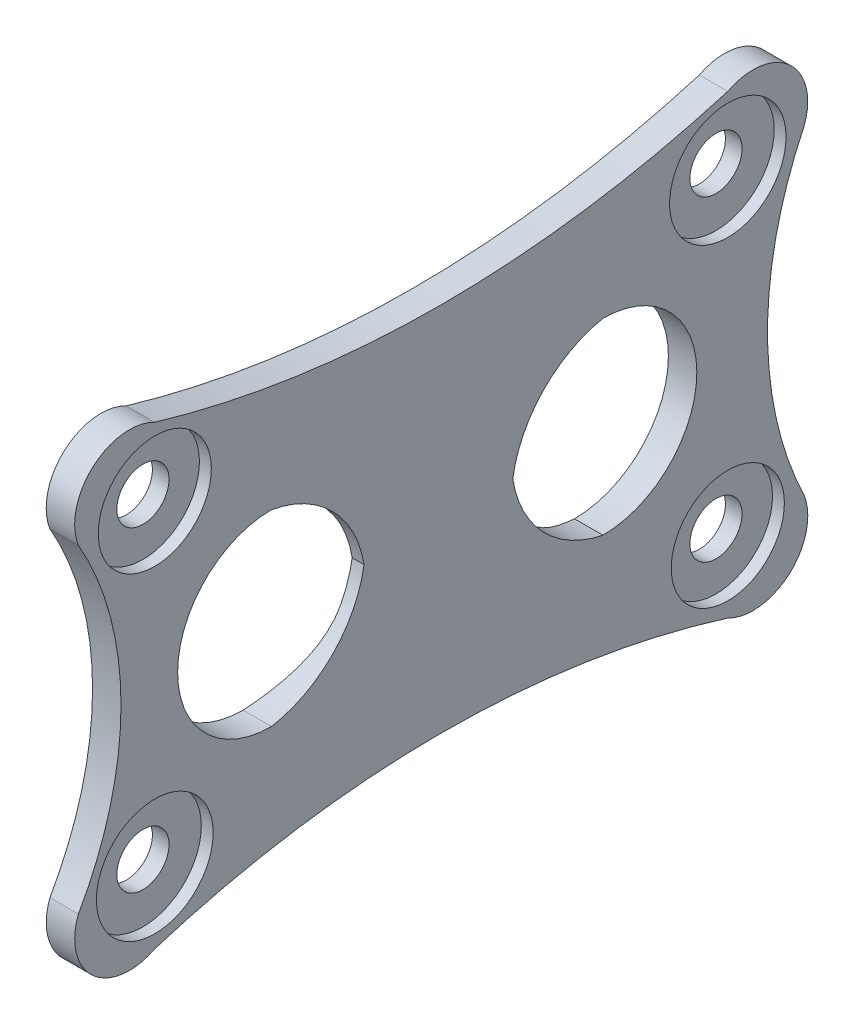
SolidWorks part; units mm, degrees
ref_plane "前视基准面" through (0, 0, 0) normal (0, 0, 1) x (1, 0, 0)
ref_plane "上视基准面" through (0, 0, 0) normal (0, 1, 0) x (1, 0, 0)
ref_plane "右视基准面" through (0, 0, 0) normal (1, 0, 0) x (0, 0, -1)
sketch "草图1" plane through (0, 0, 0) normal (1, 0, 0) x (0, 0, -1)
  line L1 (-37.5961, 46.5132) -> (45.4039, 46.5132)
  line L2 (-37.5961, 46.5132) -> (-37.5961, -12.4868)
  line L3 (-37.5961, -12.4868) -> (45.4039, -12.4868)
  line L4 (45.4039, 46.5132) -> (45.4039, -12.4868)
  line L5 (-39.5961, 48.5132) -> (47.4039, 48.5132)
  line L6 (-39.5961, 48.5132) -> (-39.5961, -14.4868)
  line L7 (-39.5961, -14.4868) -> (47.4039, -14.4868)
  line L8 (47.4039, 48.5132) -> (47.4039, -14.4868)
  dimension "D1" = 83
  dimension "D2" = 59
  dimension "D3" = 2
  dimension "D4" = 2
  dimension "D5" = 2
  dimension "D6" = 2
extrude "凸台-拉伸1" add sketch "草图1" along normal blind 5
sketch "草图2" plane through (5, 0, 0) normal (1, 0, 0) x (0, 0, -1)
  line L1 (-39.5961, 48.5132) -> (47.4039, 48.5132)
  line L2 (-39.5961, 48.5132) -> (-39.5961, -14.4868)
  line L3 (-39.5961, -14.4868) -> (47.4039, -14.4868)
  line L4 (47.4039, 48.5132) -> (47.4039, -14.4868)
extrude "凸台-拉伸2" add sketch "草图2" along normal blind 3
sketch "草图3" plane through (0, 0, -47.4039) normal (0, 0, -1) x (-1, 0, 0)
  line L1 (-5.0451, -4.4807) -> (-2.2805, -4.4807)
  line L2 (-5.0451, -4.4807) -> (-5.0451, -9.1322)
  line L3 (-5.0451, -9.1322) -> (-2.2805, -9.1322)
  line L4 (-2.2805, -4.4807) -> (-2.2805, -9.1322)
extrude "切除-拉伸1" cut sketch "草图3" against normal blind 2
fillet "圆角1" radius 2 8 edges at (4, 48.5132, -47.4039) (4, -14.4868, -47.4039) (4, -14.4868, 39.5961) (4, 48.5132, 39.5961) (8, 48.5132, -3.9039) (8, 17.0132, -47.4039) (8, -14.4868, -3.9039) (8, 17.0132, 39.5961)
sketch "草图5" plane through (5, 0, 0) normal (-1, 0, 0) x (0, 0, 1)
  line L0 (-47.4039, 17.0132) -> (-33.1302, 17.0132) construction
  line L2 (-3.9039, 48.5132) -> (-3.9039, 32.5271) construction
  line L5 (-34.1311, 33.6989) -> (26.3234, 33.6989) construction
  line L6 (-34.1311, 33.6989) -> (-34.1311, 0.3274) construction
  line L7 (-34.1311, 0.3274) -> (26.3234, 0.3274) construction
  line L8 (26.3234, 33.6989) -> (26.3234, 0.3274) construction
  line L9 (-34.1311, 33.6989) -> (26.3234, 0.3274) construction
  line L10 (-34.1311, 0.3274) -> (26.3234, 33.6989) construction
  circle A0 centre (-34.1311, 33.6989) radius 2.75
  circle A1 centre (26.3234, 33.6989) radius 2.75
  circle A2 centre (-34.1311, 0.3274) radius 2.75
  circle A3 centre (26.3234, 0.3274) radius 2.75
  point P4 (-3.9039, 17.0132)
  dimension "D1" = 5.5
  dimension "D2" = 5.5
  dimension "D3" = 5.5
  dimension "D4" = 5.5
extrude "切除-拉伸2" cut sketch "草图5" against normal blind 10
sketch "草图6" plane through (5, 0, 0) normal (-1, 0, 0) x (0, 0, 1)
  line L0 (-34.1311, 33.6989) -> (26.3407, 0) construction
  line L1 (26.3407, 0) -> (26.3407, 33.6989) construction
  line L2 (26.3407, 33.6989) -> (-34.1311, 0) construction
  line L3 (-20.9567, 16.8495) -> (14.0069, 16.8495) construction
  line L4 (-42.1749, 40.9106) -> (34.3845, 40.9106) construction
  line L5 (-42.1749, 40.9106) -> (-42.1749, -7.2117) construction
  line L6 (-42.1749, -7.2117) -> (34.3845, -7.2117) construction
  line L7 (34.3845, 40.9106) -> (34.3845, -7.2117) construction
  line L8 (-42.1749, 40.9106) -> (34.3845, -7.2117) construction
  line L9 (-42.1749, -7.2117) -> (34.3845, 40.9106) construction
  line L10 (-20.9567, 26.7536) -> (14.0069, 26.7536)
  line L11 (-20.9567, 6.9454) -> (14.0069, 6.9454)
  arc A0 (-42.1749, 33.6989) -> (-42.1749, 0) centre (-77.0616, 16.8495) cw
  arc A1 (34.3845, 0) -> (34.3845, 33.6989) centre (63.6979, 16.8495) cw
  arc A2 (-34.1311, 40.9106) -> (26.3407, 40.9106) centre (-3.8952, 142.9463) ccw
  arc A3 (-34.1311, -7.2117) -> (26.3407, -7.2117) centre (-3.8952, -104.0215) cw
  arc A4 (-42.1749, 0) -> (-34.1311, -7.2117) centre (-36.7977, -2.0941) ccw
  arc A5 (-42.1749, 33.6989) -> (-34.1311, 40.9106) centre (-36.7746, 35.7674) cw
  arc A6 (26.3407, 40.9106) -> (34.3845, 33.6989) centre (29.0066, 35.7923) cw
  arc A7 (26.3407, -7.2117) -> (34.3845, 0) centre (28.9915, -2.0765) ccw
  arc A8 (-20.9567, 26.7536) -> (-20.9567, 6.9454) centre (-20.9567, 16.8495) ccw
  arc A9 (14.0069, 6.9454) -> (14.0069, 26.7536) centre (14.0069, 16.8495) ccw
  point P5 (-3.8952, 16.8495)
  point P28 (-3.4749, 16.8495)
extrude "切除-拉伸3" cut sketch "草图6" against normal blind 10 flip side to cut
sketch "草图7" plane through (0, 0, -47.4039) normal (0, 0, -1) x (-1, 0, 0)
  line L1 (-5, 51.3712) -> (5.764, 51.3712)
  line L2 (-5, 51.3712) -> (-5, -21.7944)
  line L3 (-5, -21.7944) -> (5.764, -21.7944)
  line L4 (5.764, 51.3712) -> (5.764, -21.7944)
extrude "切除-拉伸4" cut sketch "草图7" against normal blind 125
sketch "草图8" plane through (8, 0, 0) normal (1, 0, 0) x (0, 0, -1)
  circle A0 centre (-26.3234, 33.6989) radius 5.9632
  circle A1 centre (34.1311, 33.6989) radius 6.1415
  circle A2 centre (-26.3234, 0.3274) radius 6.1575
  circle A3 centre (34.1311, 0.3274) radius 5.9672
extrude "切除-拉伸5" cut sketch "草图8" against normal blind 1.25
sketch "草图9" plane through (8, 0, 0) normal (1, 0, 0) x (0, 0, -1)
  line L1 (-4.0907, 33.0233) -> (11.2971, 33.0233)
  line L2 (-4.0907, 33.0233) -> (-4.0907, 1.0791)
  line L3 (-4.0907, 1.0791) -> (11.2971, 1.0791)
  line L4 (11.2971, 33.0233) -> (11.2971, 1.0791)
  line L5 (-4.0907, 33.0233) -> (11.2971, 1.0791) construction
  line L6 (-4.0907, 1.0791) -> (11.2971, 33.0233) construction
  point P0 (3.6032, 17.0512)
extrude "凸台-拉伸4" add sketch "草图9" against normal blind 1.25
fillet "圆角2" radius 12 6 edges at (6.75, 26.7536, -3.6032) (7.375, 6.9454, -11.2971) (6.75, 6.9454, -3.6032) (7.375, 26.7536, -11.2971) (7.375, 6.9454, 4.0907) (7.375, 26.7536, 4.0907)
